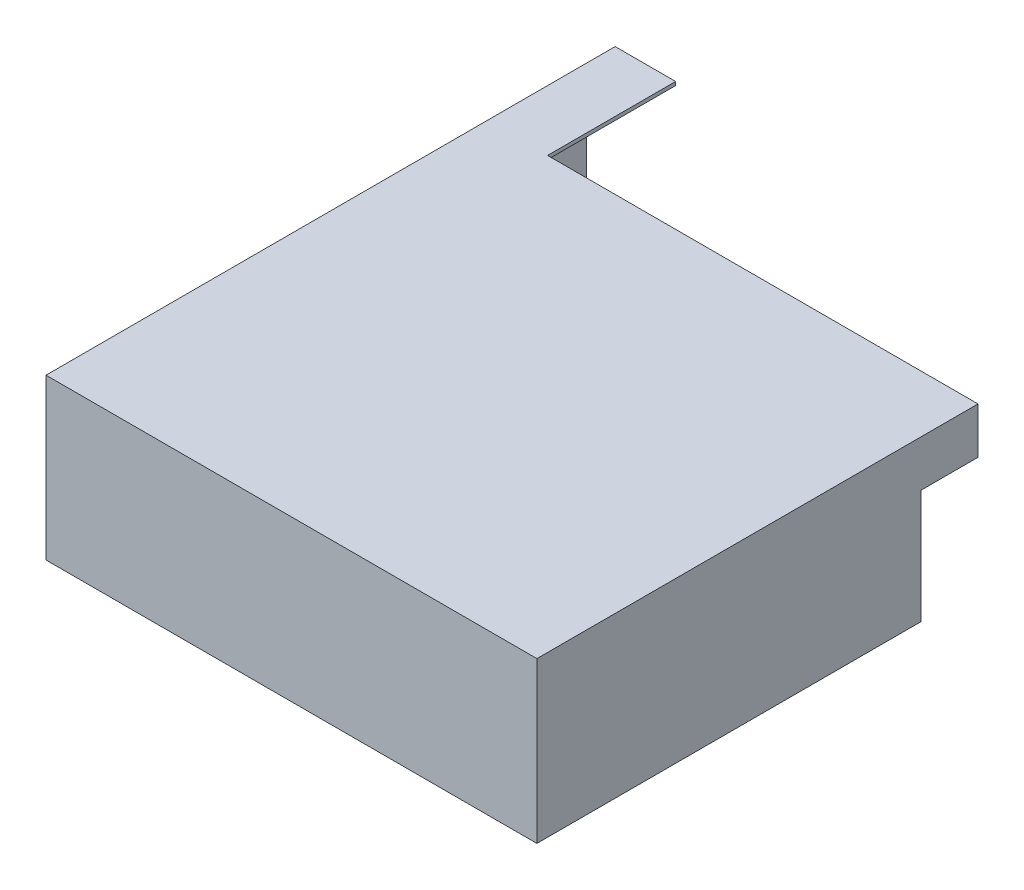
SolidWorks part; units mm, degrees
ref_plane "Front Plane" through (0, 0, 0) normal (0, 0, 1) x (1, 0, 0)
ref_plane "Top Plane" through (0, 0, 0) normal (0, 1, 0) x (1, 0, 0)
ref_plane "Right Plane" through (0, 0, 0) normal (1, 0, 0) x (0, 0, -1)
sketch "Sketch1" plane through (0, 0, 0) normal (0, 0, 1) x (1, 0, 0)
  line L0 (0, 0) -> (3.175, 0)
  line L1 (3.175, 0) -> (3.175, 139.7)
  line L2 (3.175, 139.7) -> (434.975, 139.7)
  line L3 (434.975, 139.7) -> (434.975, 0)
  line L4 (434.975, 0) -> (438.15, 0)
  line L5 (438.15, 0) -> (438.15, 142.875)
  line L6 (438.15, 142.875) -> (0, 142.875)
  line L7 (0, 142.875) -> (0, 0)
  line L8 (3.175, 139.7) -> (3.175, 142.875) construction
  dimension "D1" = 139.7
  dimension "D2" = 431.8
  dimension "D3" = 3.175
extrude "Boss-Extrude1" add sketch "Sketch1" along normal blind 508
sketch "Sketch2" plane through (0, 0, 508) normal (0, 0, 1) x (1, 0, 0)
  line L1 (0, 142.875) -> (438.15, 142.875)
  line L2 (0, 142.875) -> (0, 0)
  line L3 (0, 0) -> (438.15, 0)
  line L4 (438.15, 142.875) -> (438.15, 0)
extrude "Boss-Extrude2" add sketch "Sketch2" against normal blind 3.175
sketch "Sketch4" plane through (0, 142.875, 0) normal (0, 1, 0) x (1, 0, 0)
  line L0 (438.15, 0) -> (0, 0) construction
  line L1 (53.975, 0) -> (438.15, 0)
  line L2 (53.975, 0) -> (53.975, -114.3)
  line L3 (53.975, -114.3) -> (438.15, -114.3)
  line L4 (438.15, 0) -> (438.15, -114.3)
  line L5 (438.15, -508) -> (438.15, 0) construction
  line L6 (0, -508) -> (0, 0) construction
  dimension "D1" = 114.3
  dimension "D2" = 53.975
extrude "Cut-Extrude1" cut sketch "Sketch4" against normal through all
sketch "Sketch5" plane through (438.15, 0, 0) normal (1, 0, 0) x (0, 0, -1)
  line L1 (-114.3, 0) -> (-165.1, 0)
  line L2 (-114.3, 0) -> (-114.3, 101.6)
  line L3 (-114.3, 101.6) -> (-165.1, 101.6)
  line L4 (-165.1, 0) -> (-165.1, 101.6)
  dimension "D1" = 50.8
  dimension "D2" = 101.6
extrude "Cut-Extrude2" cut sketch "Sketch5" against normal up to next
sketch "Sketch6" plane through (0, 0, 0) normal (-1, 0, 0) x (0, 0, 1)
  line L0 (508, 142.875) -> (0, 142.875) construction
  line L1 (0, 0) -> (28.575, 0)
  line L2 (0, 0) -> (0, 117.475)
  line L3 (0, 117.475) -> (28.575, 117.475)
  line L4 (28.575, 0) -> (28.575, 117.475)
  dimension "D1" = 25.4
  dimension "D2" = 28.575
extrude "Cut-Extrude3" cut sketch "Sketch6" against normal up to next
